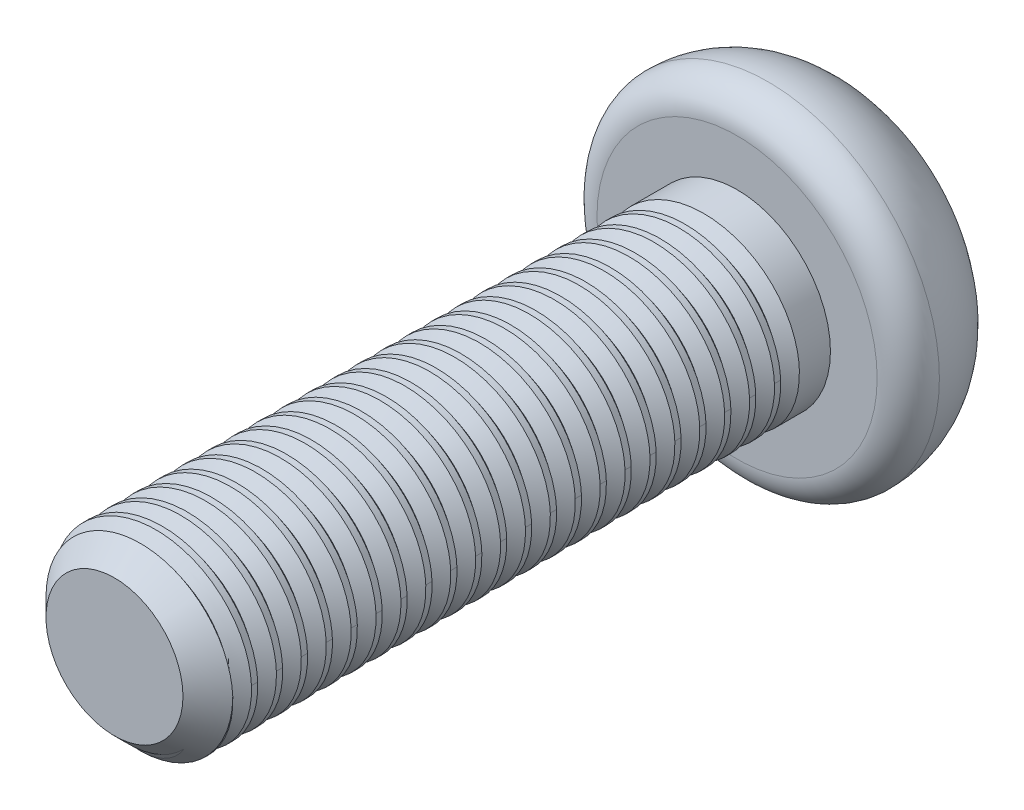
SolidWorks part; units mm, degrees
ref_plane "前视基准面" through (0, 0, 0) normal (0, 0, 1) x (1, 0, 0)
ref_plane "上视基准面" through (0, 0, 0) normal (0, 1, 0) x (1, 0, 0)
ref_plane "右视基准面" through (0, 0, 0) normal (1, 0, 0) x (0, 0, -1)
sketch "草图1" plane through (0, 0, 0) normal (0, 0, 1) x (1, 0, 0)
  circle A0 centre (0, 0) radius 5.5
  dimension "D1" = 11
extrude "凸台-拉伸1" add sketch "草图1" along normal blind 4
sketch "草图3" plane through (0, 0, 0) normal (0, 0, -1) x (-1, 0, 0)
  line L1 (1.7556, 1.5004) -> (-0.4216, 2.2706)
  line L2 (-0.4216, 2.2706) -> (-2.1772, 0.7702)
  line L3 (-2.1772, 0.7702) -> (-1.7556, -1.5004)
  line L4 (-1.7556, -1.5004) -> (0.4216, -2.2706)
  line L5 (0.4216, -2.2706) -> (2.1772, -0.7702)
  line L6 (2.1772, -0.7702) -> (1.7556, 1.5004)
  circle A0 centre (0, 0) radius 2 construction
  dimension "D1" = 4
extrude "切除-拉伸1" cut sketch "草图3" against normal blind 3
fillet "圆角1" radius 3 1 edges at (5.5, 0, 0)
fillet "圆角2" radius 1 1 edges at (5.5, 0, 4)
sketch "草图4" plane through (0, 0, 4) normal (0, 0, 1) x (1, 0, 0)
  circle A0 centre (0, 0) radius 3
  dimension "D1" = 6
extrude "凸台-拉伸2" add sketch "草图4" along normal blind 20
chamfer "倒角1" distance 0.8 angle 45 1 edges at (3, 0, 24)
sketch "草图5" plane through (0, 0, 24) normal (0, 0, 1) x (1, 0, 0)
  circle A0 centre (0, 0) radius 3
curve "螺旋线/涡状线1" pitch 0.8 height 19.2 radius 3 centre (0, 0, 24) axis (0, 0, -1) start towards (-0.7071, 0.7071, 0)
sketch "草图6" plane through (0, 0, 0) normal (1, 0, 0) x (0, 0, -1)
  line L0 (-23.6, 3) -> (-24.2, 3)
  line L1 (-24.2, 3) -> (-23.9, 2.6)
  line L2 (-23.9, 2.6) -> (-23.6, 3)
  line L4 (-23.9, 3) -> (-23.9, 2.6) construction
  dimension "D1" = 0.6
  dimension "D2" = 0.4
sweep "切除-扫描2" cut profiles "草图6" path "螺旋线/涡状线1"
